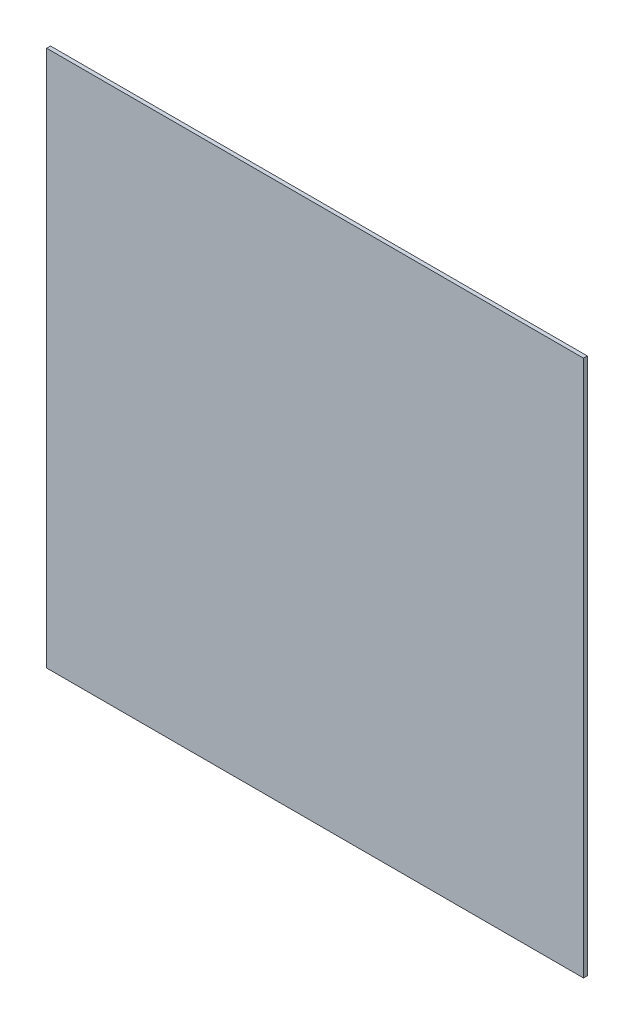
SolidWorks part; units mm, degrees
material "PE Low Density Film"
ref_plane "Front Plane" through (0, 0, 0) normal (0, 0, 1) x (1, 0, 0)
ref_plane "Top Plane" through (0, 0, 0) normal (0, 1, 0) x (1, 0, 0)
ref_plane "Right Plane" through (0, 0, 0) normal (1, 0, 0) x (0, 0, -1)
sketch "Sketch1" plane through (0, 0, 0) normal (0, 0, 1) x (1, 0, 0)
  line L4 (-79.9084, 56.1594) -> (-79.9084, 73.8886)
  line L5 (-79.9084, 73.8886) -> (-97.6376, 73.8886)
  line L6 (-97.6376, 73.8886) -> (-97.6376, 56.1594)
  line L7 (-97.6376, 56.1594) -> (-79.9084, 56.1594)
  line L8 (-79.9084, 56.1594) -> (-79.9084, 73.8886)
  line L9 (-79.9084, 73.8886) -> (-97.6376, 73.8886)
  line L10 (-97.6376, 73.8886) -> (-97.6376, 56.1594)
  line L11 (-97.6376, 56.1594) -> (-79.9084, 56.1594)
  dimension "D1" = 0
extrude "Boss-Extrude1" add sketch "Sketch1" along normal blind 0.127
